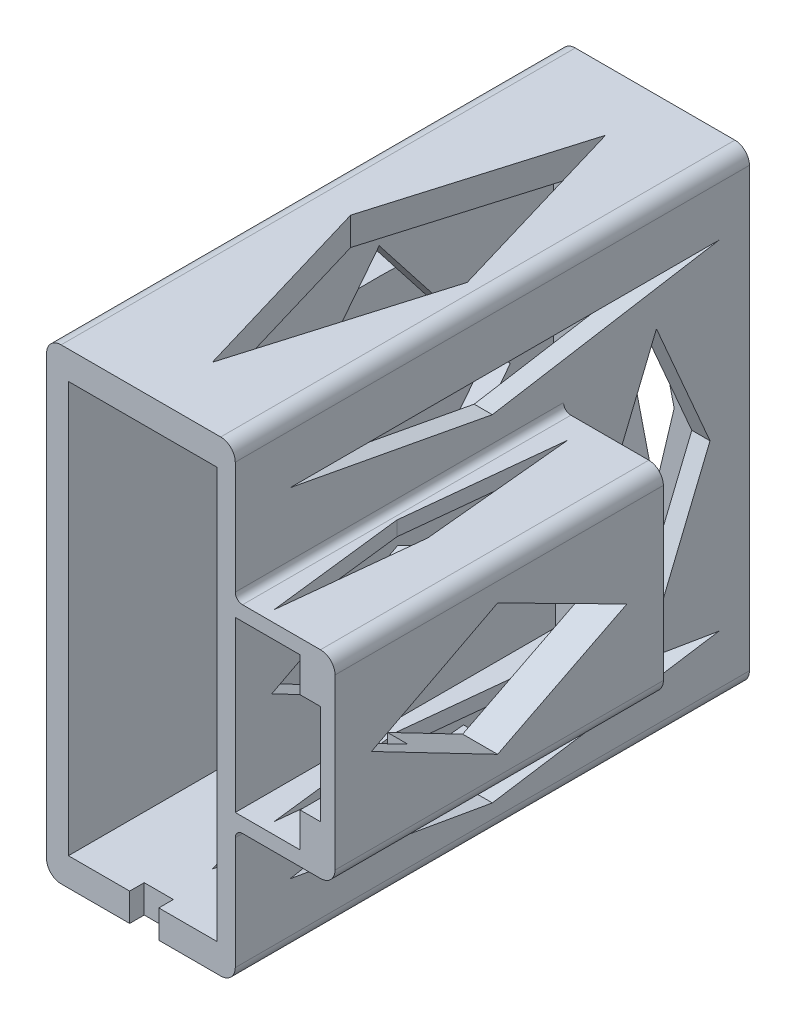
SolidWorks part; units mm, degrees
ref_plane "Front Plane" through (0, 0, 0) normal (1, 0, 0) x (0, 1, 0)
ref_plane "Top Plane" through (0, 0, 0) normal (0, 0, 1) x (0, 1, 0)
ref_plane "Right Plane" through (0, 0, 0) normal (0, 1, 0) x (-1, 0, 0)
sketch "Sketch2" plane through (0, 0, 0) normal (1, 0, 0) x (0, 1, 0)
  line L1 (-32.05, 35.3) -> (32.05, 35.3)
  line L2 (-32.05, 35.3) -> (-32.05, -35.3)
  line L3 (-32.05, -35.3) -> (32.05, -35.3)
  line L4 (32.05, 35.3) -> (32.05, -35.3)
  line L5 (-32.05, 35.3) -> (32.05, -35.3) construction
  line L6 (-32.05, -35.3) -> (32.05, 35.3) construction
  point P0 (0, 0)
  dimension "D1" = 70.6
  dimension "D2" = 64.1
extrude "Boss-Extrude1" add sketch "Sketch2" against normal blind 22.91
sketch "Sketch4" plane through (0, 0, 35.3) normal (0, 0, 1) x (1, 0, 0)
  line L0 (-22.91, 32.05) -> (-22.91, -32.05) construction
  line L1 (-23.7, 28.2) -> (-2.5, 28.2)
  line L2 (-23.7, 28.2) -> (-23.7, -28.2)
  line L3 (-23.7, -28.2) -> (-2.5, -28.2)
  line L4 (-2.5, 28.2) -> (-2.5, -28.2)
  line L7 (0, 32.05) -> (0, -32.05) construction
  point P6 (-22.91, 0)
  point P7 (-2.5, 0)
  dimension "D1" = 21.2
  dimension "D2" = 56.4
  dimension "D3" = 2.5
extrude "Cut-Extrude2" cut sketch "Sketch4" against normal blind 66.6
sketch "Sketch5" plane through (0, 0, 0) normal (1, 0, 0) x (0, 1, 0)
  line L0 (32.05, 35.3) -> (-32.05, 35.3) construction
  line L1 (-13.6, 35.3) -> (13.6, 35.3)
  line L2 (-13.6, 35.3) -> (-13.6, -1.7)
  line L3 (-13.6, -1.7) -> (13.6, -1.7)
  line L4 (13.6, 35.3) -> (13.6, -1.7)
  point P6 (0, 35.3)
  point P7 (0, 35.3)
  dimension "D1" = 37
  dimension "D2" = 27.2
extrude "Boss-Extrude2" add sketch "Sketch5" along normal blind 11.7
sketch "Sketch6" plane through (0, 0, 35.3) normal (0, 0, 1) x (1, 0, 0)
  line L0 (0, 32.05) -> (0, 13.6) construction
  line L1 (0, 11.6) -> (8.9, 11.6)
  line L2 (0, 11.6) -> (0, -11.6)
  line L3 (0, -11.6) -> (8.9, -11.6)
  line L4 (8.9, 11.6) -> (8.9, -11.6)
  line L5 (11.7, 13.6) -> (11.7, -13.6) construction
  point P9 (11.7, 0)
  point P10 (8.9, 0)
  dimension "D1" = 23.2
  dimension "D2" = 8.9
sketch "Sketch7" plane through (0, 0, -1.7) normal (0, 0, -1) x (1, 0, 0)
  line L1 (11.7, 13.6) -> (0, 13.6)
  line L2 (11.7, 13.6) -> (11.7, -13.6)
  line L3 (11.7, -13.6) -> (0, -13.6)
  line L4 (0, 13.6) -> (0, -13.6)
extrude "Boss-Extrude3" add sketch "Sketch7" along normal blind 8.08
extrude "Cut-Extrude3" cut sketch "Sketch6" against normal blind 44
sketch "Sketch8" plane through (0, 0, 35.3) normal (0, 0, 1) x (1, 0, 0)
  line L0 (0, 11.6) -> (0, -11.6) construction
  line L1 (0, 6.85) -> (12.2, 6.85)
  line L2 (0, 6.85) -> (0, -6.85)
  line L3 (0, -6.85) -> (12.2, -6.85)
  line L4 (12.2, 6.85) -> (12.2, -6.85)
  line L7 (0, 11.6) -> (0, -11.6) construction
  point P8 (0, 0)
  point P9 (12.2, 0)
  dimension "D1" = 12.2
  dimension "D2" = 13.7
extrude "Cut-Extrude4" cut sketch "Sketch8" against normal blind 12
sketch "Sketch9" plane through (0, 13.6, 0) normal (0, 1, 0) x (-1, 0, 0)
  line L0 (-3.7584, 33.72) -> (-5.7733, 14.6377)
  line L5 (-5.7733, 14.6377) -> (-3.7584, -6.5781)
  line L6 (-3.7584, -6.5781) -> (-1.5182, 14.6377)
  line L7 (-1.5182, 14.6377) -> (-3.7584, 33.72)
extrude "Cut-Extrude5" cut sketch "Sketch9" against normal up to surface (27.2 mm away) up to face at (5.85, -13.6, 12.76)
sketch "Sketch10" plane through (11.7, 0, 0) normal (1, 0, 0) x (0, 1, 0)
  line L1 (-13.6, 35.3) -> (13.6, 35.3)
  line L2 (-13.6, 35.3) -> (-13.6, -9.78)
  line L3 (-13.6, -9.78) -> (13.6, -9.78)
  line L4 (13.6, 35.3) -> (13.6, -9.78)
extrude "Boss-Extrude4" add sketch "Sketch10" along normal blind 2
sketch "Sketch11" plane through (0, -13.6, 0) normal (0, -1, 0) x (1, 0, 0)
  line L0 (13.7, -9.78) -> (0, -9.78) construction
  line L1 (3, -1.78) -> (8, -1.78)
  line L2 (3, -1.78) -> (3, 9.22)
  line L3 (3, 9.22) -> (8, 9.22)
  line L4 (8, -1.78) -> (8, 9.22)
  line L6 (0, 35.3) -> (0, -35.3) construction
  dimension "D1" = 19
  dimension "D2" = 11
  dimension "D3" = 3
  dimension "D4" = 5
extrude "Cut-Extrude6" cut sketch "Sketch11" against normal up to surface (2 mm away) up to face at (3.7021, -11.6, 14.1043)
sketch "Sketch12" plane through (0, -13.6, 0) normal (0, -1, 0) x (1, 0, 0)
  line L0 (13.7, 35.3) -> (28.5965, 35.3)
  line L1 (13.7, 35.3) -> (13.7, -9.78) construction
  line L2 (28.5965, 35.3) -> (28.5965, -0.6127)
  line L3 (28.5965, -0.6127) -> (23.5965, -0.6127)
  line L4 (23.5965, -0.6127) -> (23.5965, 26.7663)
  line L5 (23.5965, 26.7663) -> (17.3165, 26.7663)
  line L6 (17.3165, 26.7663) -> (13.7, 26.7663)
  line L7 (13.7, 26.7663) -> (13.7, 35.3)
  line L10 (13.7, 35.3) -> (0, 35.3) construction
  dimension "D1" = 6.28
  dimension "D2" = 5
  dimension "D3" = 14.8965
  dimension "D4" = 8.5337
extrude "Boss-Extrude5" add sketch "Sketch12" against normal up to surface (27.2 mm away) up to face at (3.7021, 13.6, 14.1043)
sketch "Sketch14" plane through (0, 0, 35.3) normal (0, 0, 1) x (1, 0, 0)
  line L1 (28.5965, -13.6) -> (13.7, -13.6)
  line L2 (28.5965, -13.6) -> (28.5965, -8.6)
  line L3 (28.5965, -8.6) -> (13.7, -8.6)
  line L4 (13.7, -13.6) -> (13.7, -8.6)
  line L5 (28.5965, 13.6) -> (13.7, 13.6)
  line L6 (28.5965, 13.6) -> (28.5965, 8.6)
  line L7 (28.5965, 8.6) -> (13.7, 8.6)
  line L8 (13.7, 13.6) -> (13.7, 8.6)
  dimension "D1" = 5
  dimension "D2" = 5
extrude "Cut-Extrude8" cut sketch "Sketch14" against normal up to surface (35.9127 mm away) up to face at (26.0965, 0, -0.6127)
sketch "Sketch15" plane through (28.5965, 0, 0) normal (1, 0, 0) x (0, 1, 0)
  circle A0 centre (0, 18.4305) radius 3.5
  dimension "D1" = 7
extrude "Cut-Extrude9" cut sketch "Sketch15" against normal up to surface (5 mm away) up to face at (23.5965, 0, 13.0768)
thread "Thread2" pitch 1.5 method cut profile "Thread Profile3" start angle 0, offset 1, length 10, pitch 1.5, diameter 7
ref_plane "Plane3" through (29.5965, 0, 21.9305) normal (0, -1, 0) x (0, 0, 1)
sketch "Thread Profile3" plane through (29.5965, 0, 21.9305) normal (0, -1, 0) x (0, 0, 1)
  line L0 (0, 0) -> (0, 1.5) construction
  line L1 (0, 0) -> (0.8119, 0.4687)
  line L2 (0.8119, 0.4687) -> (0.8119, 0.6562)
  line L3 (0.8119, 0.6562) -> (0, 1.125)
  line L4 (0.8119, 0.5625) -> (0, 0.5625) construction
  line L11 (0, 0) -> (0, 1.125)
  point P2 (0, 0)
  dimension "Pitch" = 1.5
  dimension "Profile_Angle" = 60
  dimension "Profile_Land" = 0.1875
  dimension "Profile_Height" = 0.8119
sketch "Sketch39" plane through (0, -32.05, 0) normal (0, -1, 0) x (1, 0, 0)
  line L0 (-11.455, 27) -> (-19.455, 0)
  line L2 (-19.455, 0) -> (-11.455, -27)
  line L4 (-11.455, -27) -> (-3.455, 0)
  line L6 (-3.455, 0) -> (-11.455, 27)
  line L7 (-22.91, 35.3) -> (-22.91, -35.3) construction
  line L8 (-22.91, 35.3) -> (0, 35.3) construction
  point P10 (-22.91, 0)
  point P16 (-11.455, 35.3)
  dimension "D1" = 8
  dimension "D2" = 8
  dimension "D3" = 27
  dimension "D4" = 27
extrude "Cut-Extrude13" cut sketch "Sketch39" against normal up to surface (64.1 mm away) up to face at (-11.455, 32.05, 0)
sketch "Sketch40" plane through (13.7, 0, 0) normal (1, 0, 0) x (0, 1, 0)
  line L0 (0, -4.78) -> (9, 12.9763)
  line L1 (9, 12.9763) -> (0, 30.3)
  line L2 (0, 30.3) -> (-9, 12.9763)
  line L3 (-9, 12.9763) -> (0, -4.78)
  line L4 (-13.6, -9.78) -> (13.6, -9.78) construction
  line L6 (-13.6, 35.3) -> (-13.6, -9.78) construction
  line L7 (13.6, -9.78) -> (13.6, 35.3) construction
  line L8 (8.6, 35.3) -> (-8.6, 35.3) construction
  point P2 (0, 0)
  point P5 (0, -9.78)
  dimension "D1" = 5
  dimension "D2" = 9
  dimension "D3" = 5
  dimension "D4" = 27.2
  dimension "D6" = 9
  dimension "D7" = 17.3237
extrude "Cut-Extrude14" cut sketch "Sketch40" against normal up to surface (4.8 mm away) up to face at (8.9, 0, 21.3)
sketch "Sketch41" plane through (0, 0, -9.78) normal (0, 0, -1) x (1, 0, 0)
  line L0 (0, 13.6) -> (0, -13.6) construction
  line L1 (0, 6.119) -> (7, 6.119)
  line L2 (0, 6.119) -> (0, -6.119)
  line L3 (0, -6.119) -> (7, -6.119)
  line L4 (7, 6.119) -> (7, -6.119)
  point P6 (7, 0)
  dimension "D1" = 7
extrude "Cut-Extrude15" cut sketch "Sketch41" against normal up to surface (1.08 mm away) up to face at (4.45, 0, -8.7)
sketch "Sketch42" plane through (0, 0, -35.3) normal (0, 0, -1) x (1, 0, 0)
  line L0 (-11.455, 21.5394) -> (-16.5757, 0)
  line L5 (-16.5757, 0) -> (-11.455, -21.5394)
  line L6 (-11.455, -21.5394) -> (-6.3343, 0)
  line L7 (-6.3343, 0) -> (-11.455, 21.5394)
extrude "Cut-Extrude16" cut sketch "Sketch42" against normal up to surface (4 mm away) up to face at (-12.705, 0, -31.3)
sketch "Sketch44" plane through (0, 0, 35.3) normal (0, 0, 1) x (1, 0, 0)
  line L0 (-22.91, -28.2) -> (-2.5, -28.2) construction
  line L1 (-14.5, -28.2) -> (-10.5, -28.2)
  line L2 (-14.5, -28.2) -> (-14.5, -32.05)
  line L3 (-14.5, -32.05) -> (-10.5, -32.05)
  line L4 (-10.5, -28.2) -> (-10.5, -32.05)
  line L5 (-22.91, -32.05) -> (0, -32.05) construction
  line L6 (0, -13.6) -> (0, -32.05) construction
  point P8 (-12.5, -28.2)
  dimension "D1" = 4
  dimension "D2" = 12.5
extrude "Cut-Extrude17" cut sketch "Sketch44" against normal blind 2
fillet "Fillet1" radius 2 4 edges at (0, 32.05, 0) (13.7, 13.6, 12.76) (13.7, -13.6, 12.76) (0, -32.05, 0)
sketch "Sketch45" plane through (0, -8.6, 0) normal (0, -1, 0) x (1, 0, 0)
  line L1 (13.7, 35.3) -> (50.7967, 35.3)
  line L2 (13.7, 35.3) -> (13.7, -11.6173)
  line L3 (13.7, -11.6173) -> (50.7967, -11.6173)
  line L4 (50.7967, 35.3) -> (50.7967, -11.6173)
extrude "Cut-Extrude18" cut sketch "Sketch45" against normal up to surface (17.2 mm away) up to face at (21.9643, 8.6, 20.4845)
sketch "Sketch46" plane through (-22.91, 0, 0) normal (-1, 0, 0) x (0, -1, 0)
  line L1 (-32.05, 35.3) -> (32.05, 35.3)
  line L2 (-32.05, 35.3) -> (-32.05, -35.3)
  line L3 (-32.05, -35.3) -> (32.05, -35.3)
  line L4 (32.05, 35.3) -> (32.05, -35.3)
extrude "Boss-Extrude6" add sketch "Sketch46" along normal blind 5
sketch "Sketch48" plane through (-27.91, 0, 0) normal (-1, 0, 0) x (0, 0, 1)
  line L1 (35.3, 32.05) -> (-35.3, 32.05)
  line L2 (35.3, 32.05) -> (35.3, -32.05)
  line L3 (35.3, -32.05) -> (-35.3, -32.05)
  line L4 (-35.3, 32.05) -> (-35.3, -32.05)
extrude "Boss-Extrude7" add sketch "Sketch48" along normal blind 5
ref_plane "Plane4" through (0, 0, 25.3) normal (0, 0, 1) x (1, 0, 0)
sketch "Sketch52" plane through (0, 0, 25.3) normal (0, 0, 1) x (1, 0, 0)
  line L0 (-32.91, -2.5) -> (-32.41, -2.5)
  line L1 (-32.91, 2.5) -> (-32.41, 2.5)
  line L2 (-32.91, -32.05) -> (-32.91, 32.05) construction
  line L3 (-32.91, -2.5) -> (-32.91, 2.5)
  arc A0 (-32.41, -2.5) -> (-27.4316, -2.4209) centre (-29.9599, 0) ccw
  arc A5 (-32.41, 2.5) -> (-27.4316, 2.4209) centre (-29.9599, 0) cw
  arc A6 (-27.4316, 2.4209) -> (-27.4316, -2.4209) centre (-29.9599, 0) cw
  point P6 (-29.9043, -3.5)
  point P13 (-29.9043, 3.5)
  point P14 (-32.91, 0)
  point P15 (-32.91, 0)
  dimension "D3" = 0.5
  dimension "D5" = 1
  dimension "D4" = 0.5
  dimension "D6" = 1
  dimension "D7" = 5
extrude "Cut-Extrude19" cut sketch "Sketch52" against normal blind 4 and the other way blind 3.5
chamfer "Chamfer1" distance 0.2 angle 45 2 edges at (-32.91, -2.5, 25.05) (-32.91, 2.5, 25.05)
sketch "Sketch53" plane through (-32.91, 0, 0) normal (-1, 0, 0) x (0, -1, 0)
  line L1 (-4.2243, 29.3944) -> (4.6468, 29.3944)
  line L2 (-4.2243, 29.3944) -> (-4.2243, 19.96)
  line L3 (-4.2243, 19.96) -> (4.6468, 19.96)
  line L4 (4.6468, 29.3944) -> (4.6468, 19.96)
extrude "Boss-Extrude8" add sketch "Sketch53" against normal up to surface (10 mm away) up to face at (-22.91, 0, 2)
sketch "Sketch54" plane through (0, 0, 35.3) normal (0, 0, 1) x (1, 0, 0)
  line L0 (-32.91, 32.05) -> (-2, 32.05) construction
  line L1 (-2.5, 28.2) -> (-22.91, 28.2) construction
  line L2 (-2.5, -28.2) -> (-2.5, 28.2) construction
  line L3 (0, 30.05) -> (0, 13.6) construction
  line L4 (-32.91, -32.05) -> (-14.5, -32.05) construction
  line L5 (-32.91, 32.05) -> (-25.91, 32.05)
  line L6 (-32.91, 32.05) -> (-32.91, -32.05)
  line L7 (-32.91, -32.05) -> (-25.91, -32.05)
  line L8 (-25.91, 32.05) -> (-25.91, -32.05)
  line L9 (-22.91, 28.2) -> (-22.91, -28.2) construction
  dimension "D1" = 3.85
  dimension "D2" = 2.5
  dimension "D3" = 3
extrude "Cut-Extrude20" cut sketch "Sketch54" against normal up to surface (70.6 mm away) up to face at (-11.455, 0, -35.3)
fillet "Fillet2" radius 2 2 edges at (-25.91, -32.05, 0) (-25.91, 32.05, 0)
fillet "Fillet3" radius 1 2 edges at (0, -13.6, 12.76) (0, 13.6, 12.76)
ref_plane "Plane5" through (0, 0, 0) normal (0, -1, 0) x (-1, 0, 0)
sketch "Sketch55" plane through (0, 0, 0) normal (0, -1, 0) x (-1, 0, 0)
  line L0 (25.91, -31.2082) -> (29.5237, -31.2082)
  line L1 (25.91, 35.3) -> (25.91, -35.3) construction
  line L3 (29.5237, 31.8042) -> (25.91, 31.8042)
  line L5 (25.91, -11.2082) -> (25.91, -31.2082)
  arc A0 (25.91, 31.8042) -> (25.91, -11.2082) centre (-145.6435, 10.298) cw
  arc A1 (29.5237, 31.8042) -> (29.5237, -31.2082) centre (-419.5596, 0.298) cw
  dimension "D1" = 20
extrude "Boss-Extrude10" add sketch "Sketch55" along normal blind 15 and the other way blind 15 separate body
sketch "Sketch56" plane through (0, -15, 0) normal (0, -1, 0) x (1, 0, 0)
  line L3 (-25.91, -35.3) -> (-25.91, 35.3) construction
  line L4 (-25.91, 14.5082) -> (-25.91, 11.2082)
  line L5 (-25.91, 11.2082) -> (-26.3102, 7.7312)
  arc A2 (-26.3102, 7.7312) -> (-25.91, 14.5082) centre (-24.5633, 11.0284) cw
  arc A3 (-25.91, 11.2082) -> (-25.91, -31.8042) centre (145.6435, -10.298) ccw construction
  dimension "D1" = 3.3
  dimension "D2" = 3.5
extrude "Cut-Extrude21" cut sketch "Sketch56" against normal up to surface (30 mm away) up to face at (-27.8448, 15, 2.0033)
sketch "Sketch58" plane through (-25.91, 0, 0) normal (-1, 0, 0) x (0, -1, 0)
  line L0 (0, 10.6235) -> (-23, -7.3765)
  line L1 (-23, -7.3765) -> (0, -25.3765)
  line L2 (0, -25.3765) -> (23, -7.3765)
  line L3 (23, -7.3765) -> (0, 10.6235)
  line L4 (30.05, 35.3) -> (-30.05, 35.3) construction
  point P6 (0, 35.3)
  dimension "D1" = 23
  dimension "D2" = 23
  dimension "D3" = 18
  dimension "D4" = 18
extrude "Cut-Extrude22" cut sketch "Sketch58" against normal up to surface (3 mm away) up to face at (-22.91, 0, 2)
sketch "Sketch59" plane through (0, 0, 0) normal (1, 0, 0) x (0, 1, 0)
  line L0 (0, 30.3) -> (-9, 12.9763)
  line L1 (-9, 12.9763) -> (0, -4.78)
  line L2 (0, -4.78) -> (9, 12.9763)
  line L3 (9, 12.9763) -> (0, 30.3)
extrude "Cut-Extrude23" cut sketch "Sketch59" against normal up to surface (2.5 mm away) up to face at (-2.5, 0, 2)
sketch "Sketch60" plane through (0, 0, 0) normal (1, 0, 0) x (0, 1, 0)
  line L0 (23.25, 27.7781) -> (18.0502, 0)
  line L1 (18.0502, 0) -> (23.25, -31.1319)
  line L2 (23.25, -31.1319) -> (23.25, 0)
  line L3 (23.25, 0) -> (23.25, 27.7781)
  line L5 (-23.25, -31.1319) -> (-28.114, 0)
  line L6 (-18.0502, 0) -> (-23.25, -31.1319)
  line L7 (-23.25, 27.7781) -> (-18.0502, 0)
  line L8 (-28.114, 0) -> (-23.25, 27.7781)
  line L9 (0, -15.5295) -> (-17, -22.8878)
  line L10 (-17, -22.8878) -> (0, -29.8878)
  line L11 (0, -29.8878) -> (17, -22.5295)
  line L12 (17, -22.5295) -> (0, -15.5295)
  point P4 (23.25, -0.739)
  point P5 (-28.114, 0)
  point P15 (23.25, 0)
  point P16 (23.25, 0)
  dimension "D1" = 17
  dimension "D2" = 17
  dimension "D3" = 7
  dimension "D4" = 7
extrude "Cut-Extrude24" cut sketch "Sketch60" against normal up to surface (2.5 mm away) up to face at (-2.5, 0, 12.8681)
sketch "Sketch61" plane through (0, -15, 0) normal (0, -1, 0) x (1, 0, 0)
  line L0 (-26.481, -31.8042) -> (-26.481, -26.6157)
  line L1 (-29.5237, -31.8042) -> (-25.91, -31.8042) construction
  line L2 (-26.481, -26.6157) -> (-25.91, -27.1086)
  line L3 (-25.91, -35.3) -> (-25.91, 35.3) construction
  line L4 (-25.91, -27.1086) -> (-25.91, -34.0585)
  line L5 (-25.91, -34.0585) -> (-26.481, -31.8042)
  arc A0 (-26.3102, 7.7312) -> (-25.91, -31.8042) centre (145.6435, -10.298) ccw construction
extrude "Cut-Extrude25" cut sketch "Sketch61" against normal up to surface (30 mm away) up to face at (-27.9172, 15, 3.5274)
